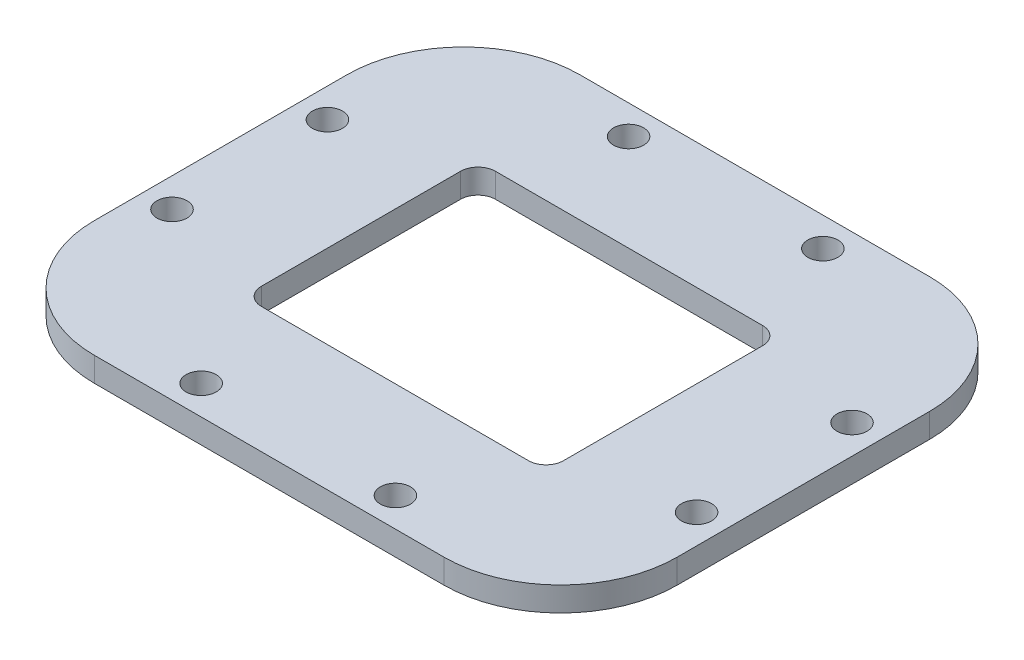
SolidWorks part; units mm, degrees
material "ABS"
ref_plane "前视基准面" through (0, 0, 0) normal (0, 0, 1) x (1, 0, 0)
ref_plane "上视基准面" through (0, 0, 0) normal (0, 1, 0) x (1, 0, 0)
ref_plane "右视基准面" through (0, 0, 0) normal (1, 0, 0) x (0, 0, -1)
other "Configuration Table"
sketch "草图1" plane through (0, 0, 0) normal (0, 1, 0) x (1, 0, 0)
  line L1 (-30, 25) -> (30, 25)
  line L2 (-30, 25) -> (-30, -25)
  line L3 (-30, -25) -> (30, -25)
  line L4 (30, 25) -> (30, -25)
  line L5 (-30, 25) -> (30, -25) construction
  line L6 (-30, -25) -> (30, 25) construction
  line L7 (-14.75, 11.25) -> (14.75, 11.25)
  line L8 (-14.75, 11.25) -> (-14.75, -11.25)
  line L9 (-14.75, -11.25) -> (14.75, -11.25)
  line L10 (14.75, 11.25) -> (14.75, -11.25)
  line L11 (-14.75, 11.25) -> (14.75, -11.25) construction
  line L12 (-14.75, -11.25) -> (14.75, 11.25) construction
  point P0 (0, 0)
  point P6 (0, 0)
  dimension "D1" = 60
  dimension "D2" = 50
  dimension "D3" = 29.5
  dimension "D4" = 22.5
extrude "凸台-拉伸1" add sketch "草图1" along normal blind 2.5
sketch "草图8" plane through (0, 0, 0) normal (0, -1, 0) x (1, 0, 0)
  line L0 (0, 25) -> (0, 0) construction
  line L1 (-30, 25) -> (30, 25) construction
  line L2 (0, 0) -> (30, 0) construction
  line L3 (30, 25) -> (30, -25) construction
  line L4 (-10, 22) -> (10, 22) construction
  circle A0 centre (27, 8) radius 1.55
  circle A1 centre (10, 22) radius 1.55
  circle A2 centre (-10, 22) radius 1.55
  circle A3 centre (-27, 8) radius 1.55
  circle A4 centre (-27, -8) radius 1.55
  circle A5 centre (-10, -22) radius 1.55
  circle A6 centre (10, -22) radius 1.55
  circle A7 centre (27, -8) radius 1.55
  dimension "D1" = 44
  dimension "D2" = 54
  dimension "D3" = 3.1
  dimension "D4" = 20
  dimension "D5" = 16
extrude "切除-拉伸2" cut sketch "草图8" against normal blind 10
fillet "圆角1" radius 1 4 edges at (-14.75, 1.25, 11.25) (14.75, 1.25, 11.25) (14.75, 1.25, -11.25) (-14.75, 1.25, -11.25)
fillet "圆角2" radius 12 4 edges at (30, 1.25, 25) (-30, 1.25, -25) (30, 1.25, -25) (-30, 1.25, 25)
sketch "草图9" plane through (0, 0, 0) normal (0, -1, 0) x (1, 0, 0)
  line L0 (14.75, 10.25) -> (14.75, -10.25) construction
  line L1 (13.75, -11.25) -> (-13.75, -11.25) construction
  line L2 (-14.75, -10.25) -> (-14.75, 10.25) construction
  line L3 (-13.75, 11.25) -> (13.75, 11.25) construction
  line L12 (14.75, 10.25) -> (14.75, -10.25) construction
  line L13 (13.75, -11.25) -> (-13.75, -11.25) construction
  line L14 (-14.75, -10.25) -> (-14.75, 10.25) construction
  line L15 (-13.75, 11.25) -> (13.75, 11.25) construction
  line L16 (-13.75, 12.05) -> (13.75, 12.05)
  line L17 (-15.55, -10.25) -> (-15.55, 10.25)
  line L18 (13.75, -12.05) -> (-13.75, -12.05)
  line L19 (15.55, 10.25) -> (15.55, -10.25)
  arc A0 (14.75, 10.25) -> (13.75, 11.25) centre (13.75, 10.25) ccw construction
  arc A1 (13.75, -11.25) -> (14.75, -10.25) centre (13.75, -10.25) ccw construction
  arc A2 (-14.75, -10.25) -> (-13.75, -11.25) centre (-13.75, -10.25) ccw construction
  arc A3 (-13.75, 11.25) -> (-14.75, 10.25) centre (-13.75, 10.25) ccw construction
  arc A12 (14.75, 10.25) -> (13.75, 11.25) centre (13.75, 10.25) ccw construction
  arc A13 (13.75, -11.25) -> (14.75, -10.25) centre (13.75, -10.25) ccw construction
  arc A14 (-14.75, -10.25) -> (-13.75, -11.25) centre (-13.75, -10.25) ccw construction
  arc A15 (-13.75, 11.25) -> (-14.75, 10.25) centre (-13.75, 10.25) ccw construction
  arc A16 (15.55, 10.25) -> (13.75, 12.05) centre (13.75, 10.25) ccw
  arc A17 (-13.75, 12.05) -> (-15.55, 10.25) centre (-13.75, 10.25) ccw
  arc A18 (-15.55, -10.25) -> (-13.75, -12.05) centre (-13.75, -10.25) ccw
  arc A19 (13.75, -12.05) -> (15.55, -10.25) centre (13.75, -10.25) ccw
  dimension "D1" = 0.8
extrude "切除-拉伸3" cut sketch "草图9" against normal blind 10
